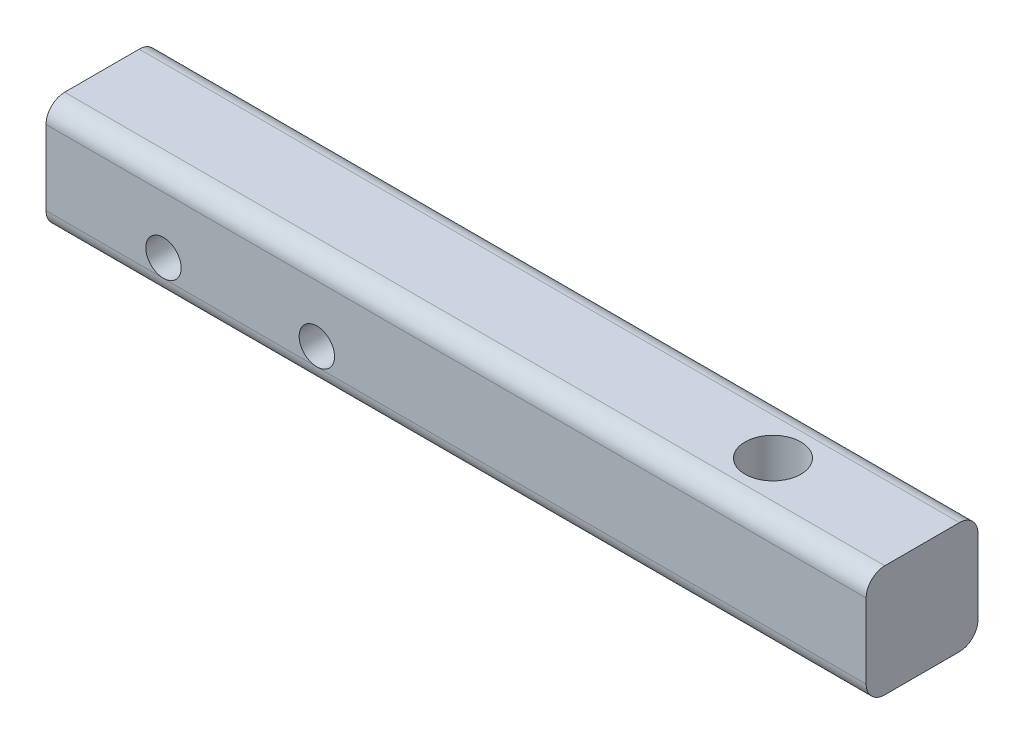
SolidWorks part; units mm, degrees
ref_plane "Front Plane" through (0, 0, 0) normal (0, 0, 1) x (1, 0, 0)
ref_plane "Top Plane" through (0, 0, 0) normal (0, 1, 0) x (1, 0, 0)
ref_plane "Right Plane" through (0, 0, 0) normal (1, 0, 0) x (0, 0, -1)
sketch "Sketch1" plane through (0, 0, 0) normal (1, 0, 0) x (0, 0, -1)
  line L1 (-9.525, -9.525) -> (9.525, -9.525)
  line L2 (-9.525, -9.525) -> (-9.525, 9.525)
  line L3 (-9.525, 9.525) -> (9.525, 9.525)
  line L4 (9.525, -9.525) -> (9.525, 9.525)
  line L5 (-9.525, -9.525) -> (9.525, 9.525) construction
  line L6 (-9.525, 9.525) -> (9.525, -9.525) construction
  point P0 (0, 0)
  dimension "D1" = 19.05
extrude "Boss-Extrude1" add sketch "Sketch1" along normal blind 139.7 contours L2 L3 L4 L1
sketch "Sketch2" plane through (0, 9.525, 0) normal (0, 1, 0) x (1, 0, 0)
  line L0 (139.7, -9.525) -> (139.7, 9.525) construction
  circle A0 centre (114.3, 0) radius 4.7625
  dimension "D1" = 9.525
  dimension "D2" = 25.4
extrude "Cut-Extrude1" cut sketch "Sketch2" against normal through all
sketch "Sketch3" plane through (0, 0, 9.525) normal (0, 0, 1) x (1, 0, 0)
  circle A0 centre (20.0078, -3.3156) radius 3.013
  circle A1 centre (46.1339, -3.3156) radius 3.013
extrude "Cut-Extrude2" cut sketch "Sketch3" against normal through all
fillet "Fillet1" radius 3.175 4 edges at (69.85, -9.525, -9.525) (69.85, -9.525, 9.525) (69.85, 9.525, -9.525) (69.85, 9.525, 9.525)
